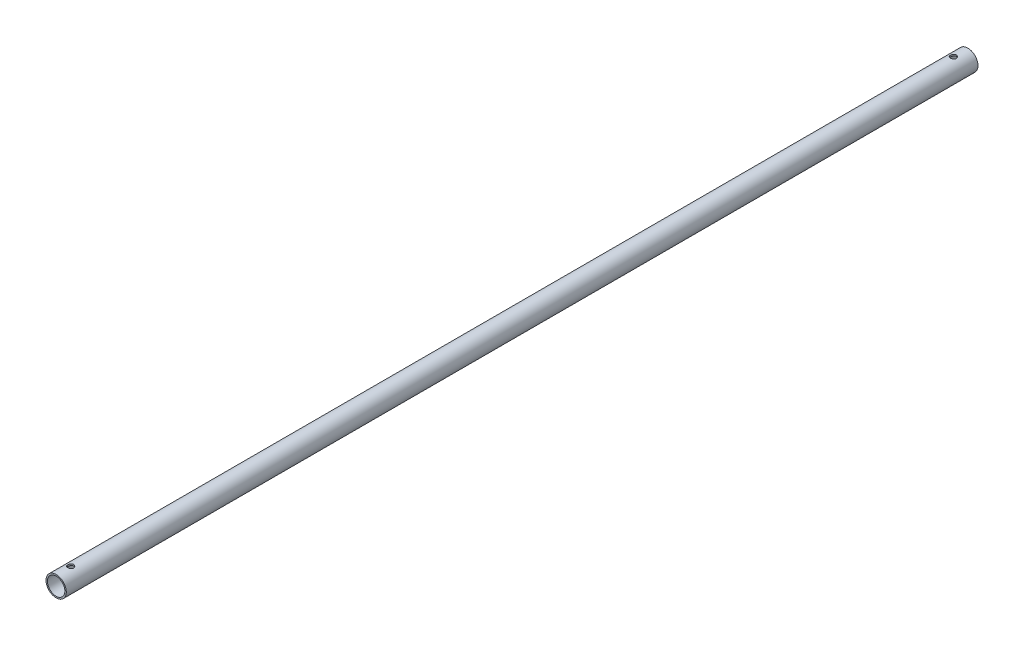
SolidWorks part; units mm, degrees
material "Hexcel AS4C (3000 Filaments)"
ref_plane "Plan de face" through (0, 0, 0) normal (0, 0, 1) x (1, 0, 0)
ref_plane "Plan de dessus" through (0, 0, 0) normal (0, 1, 0) x (1, 0, 0)
ref_plane "Plan de droite" through (0, 0, 0) normal (1, 0, 0) x (0, 0, -1)
sketch "Esquisse1" plane through (0, 0, 0) normal (0, 0, 1) x (1, 0, 0)
  circle A0 centre (0, 0) radius 3.5
  circle A1 centre (0, 0) radius 3
  dimension "D1" = 6
  dimension "D2" = 7
extrude "Boss.-Extru.1" add sketch "Esquisse1" along normal blind 314
sketch "Esquisse2" plane through (0, 0, 0) normal (0, 1, 0) x (1, 0, 0)
  line L0 (-3.5, -314) -> (3.5, -314) construction
  line L1 (-3.5, 0) -> (-3.5, -314) construction
  line L2 (3.5, -314) -> (3.5, 0) construction
  line L3 (3.5, 0) -> (-3.5, 0) construction
  circle A0 centre (0, -309) radius 1
  circle A1 centre (0, -5) radius 1
  dimension "D2" = 2
  dimension "D6" = 2
  dimension "D1" = 5
  dimension "D3" = 3.5
  dimension "D4" = 3.5
  dimension "D5" = 5
extrude "Enlèv. mat.-Extru.1" cut sketch "Esquisse2" against normal blind 10 and the other way blind 10
